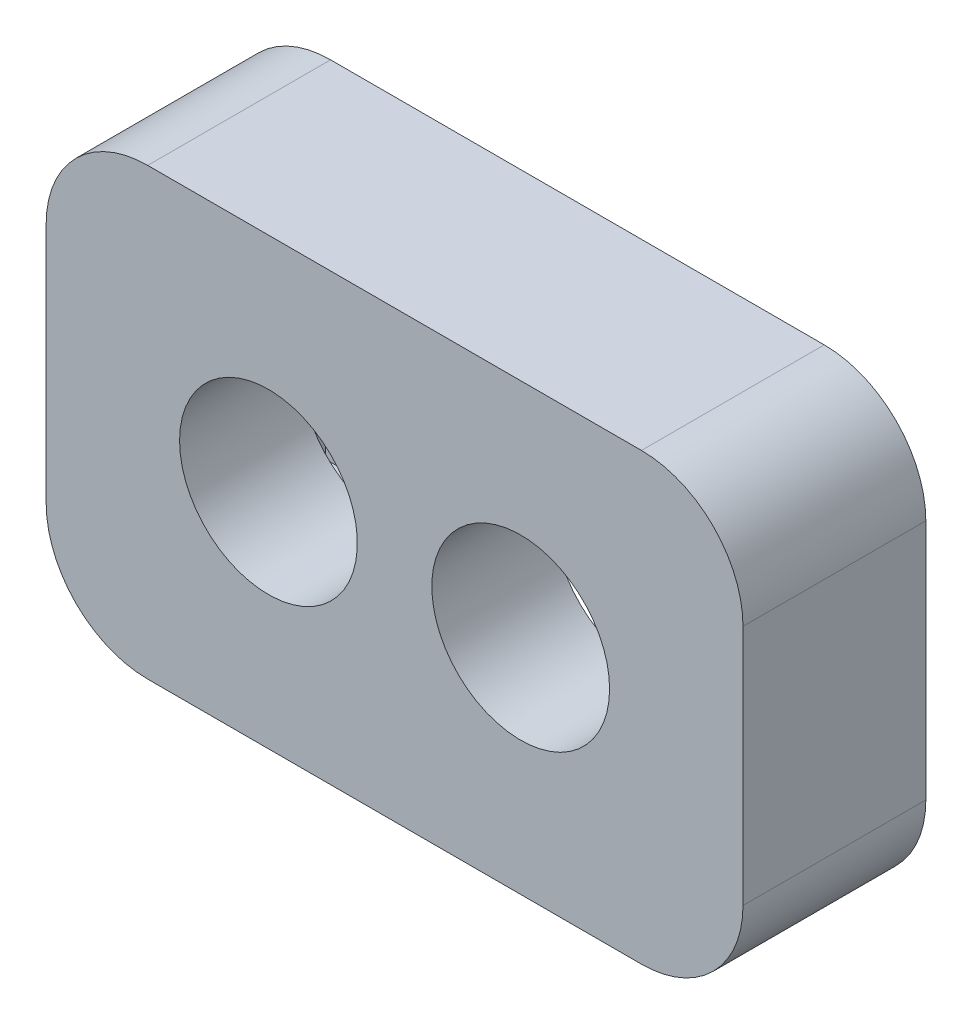
SolidWorks part; units mm, degrees
ref_plane "Front Plane" through (0, 0, 0) normal (0, 0, 1) x (1, 0, 0)
ref_plane "Top Plane" through (0, 0, 0) normal (0, 1, 0) x (1, 0, 0)
ref_plane "Right Plane" through (0, 0, 0) normal (1, 0, 0) x (0, 0, -1)
sketch "Sketch1" plane through (0, 0, 0) normal (0, 0, 1) x (1, 0, 0)
  line L0 (-22.8, 10.4) -> (-22.8, -10.4) construction
  line L1 (-34.3, -21.9) -> (34.3, -21.9)
  line L2 (-34.3, -21.9) -> (-34.3, 21.9)
  line L3 (-34.3, 21.9) -> (34.3, 21.9)
  line L4 (34.3, -21.9) -> (34.3, 21.9)
  line L5 (-34.3, -21.9) -> (34.3, 21.9) construction
  line L6 (-34.3, 21.9) -> (34.3, -21.9) construction
  line L7 (-22.8, -10.4) -> (22.8, -10.4) construction
  line L8 (0, 15.7444) -> (0, -21.2968) construction
  circle A1 centre (12.416, 0) radius 8.75
  circle A2 centre (-12.416, 0) radius 8.75
  point P0 (0, 0)
  dimension "D3" = 17.5
  dimension "D1" = 11.5
  dimension "D2" = 11.5
extrude "Boss-Extrude1" add sketch "Sketch1" along a picked direction on the side of the normal blind 12
sketch "Sketch2" plane through (0, 0, 0) normal (0, 0, -1) x (-1, 0, 0)
  line L0 (3.175, 6) -> (-3.175, 6) construction
  line L1 (-3.175, 10.25) -> (3.175, 10.25) construction
  line L2 (3.175, 6) -> (-3.175, 6)
  line L3 (-3.175, 10.25) -> (3.175, 10.25)
  arc A0 (-3.175, 10.25) -> (-3.175, 6) centre (-3.175, 8.125) ccw construction
  arc A1 (3.175, 6) -> (3.175, 10.25) centre (3.175, 8.125) ccw construction
  arc A2 (-3.175, 10.25) -> (-3.175, 6) centre (-3.175, 8.125) ccw
  arc A3 (3.175, 6) -> (3.175, 10.25) centre (3.175, 8.125) ccw
extrude "Cut-Extrude1" cut sketch "Sketch2" against normal up to vertex (3.35 mm away)
sketch "Sketch3" plane through (0, 0, 0) normal (0, 0, -1) x (-1, 0, 0)
  line L0 (22.8, -10.4) -> (-22.8, -10.4) construction
  line L1 (-22.8, -10.4) -> (-22.8, 10.4) construction
  line L2 (-22.8, 10.4) -> (22.8, 10.4) construction
  line L3 (22.8, 10.4) -> (22.8, -10.4) construction
  line L4 (22.8, -10.4) -> (-22.8, -10.4)
  line L5 (-22.8, -10.4) -> (-22.8, 10.4)
  line L6 (-22.8, 10.4) -> (22.8, 10.4)
  line L7 (22.8, 10.4) -> (22.8, -10.4)
  line L8 (34.3, -21.9) -> (-34.3, -21.9) construction
  line L9 (-34.3, -21.9) -> (-34.3, 21.9) construction
  line L10 (-34.3, 21.9) -> (34.3, 21.9) construction
  line L11 (34.3, 21.9) -> (34.3, -21.9) construction
  line L12 (34.3, -21.9) -> (-34.3, -21.9)
  line L13 (-34.3, -21.9) -> (-34.3, 21.9)
  line L14 (-34.3, 21.9) -> (34.3, 21.9)
  line L15 (34.3, 21.9) -> (34.3, -21.9)
extrude "Boss-Extrude2" add sketch "Sketch3" along normal blind 6
fillet "Fillet1" radius 10 4 edges at (34.3, 21.9, 3) (34.3, -21.9, 3) (-34.3, -21.9, 3) (-34.3, 21.9, 3)
sketch "Sketch4" plane through (0, 0, -6) normal (0, 0, -1) x (-1, 0, 0)
  line L0 (0, 23.8651) -> (0, -24.5579) construction
  line L1 (0, 0) -> (-37.2603, 0) construction
  circle A0 centre (27, 14.6) radius 5.2
  circle A1 centre (-27, 14.6) radius 5.2
  circle A2 centre (27, -14.6) radius 5.2
  circle A3 centre (-27, -14.6) radius 5.2
  dimension "D1" = 10.4
  dimension "D2" = 7.3
  dimension "D3" = 7.3
extrude "Cut-Extrude2" cut sketch "Sketch4" against normal blind 2.3
sketch "Sketch6" plane through (0, 0, -6) normal (0, 0, -1) x (-1, 0, 0)
  line L0 (-22.8, -10.4) -> (22.8, -10.4) construction
  line L1 (-22.8, 10.4) -> (-22.8, -10.4) construction
  line L2 (22.8, 10.4) -> (-22.8, 10.4) construction
  line L3 (22.8, -10.4) -> (22.8, 10.4) construction
  line L4 (-22.8, -10.4) -> (-7.275, -10.4)
  line L5 (-22.8, 10.4) -> (-22.8, -10.4)
  line L6 (22.8, 10.4) -> (-22.8, 10.4)
  line L7 (22.8, -10.4) -> (22.8, 10.4)
  line L8 (-21.8, -9.4) -> (-7.275, -9.4)
  line L9 (21.8, -9.4) -> (21.8, 9.4)
  line L10 (21.8, 9.4) -> (-21.8, 9.4)
  line L11 (-21.8, 9.4) -> (-21.8, -9.4)
  line L12 (-7.275, -7.95) -> (-7.275, -10.3) construction
  line L13 (7.275, -10.3) -> (7.275, -7.95) construction
  line L14 (-7.275, -9.4) -> (-7.275, -10.4)
  line L15 (7.275, -10.4) -> (7.275, -9.4)
  line L16 (7.275, -9.4) -> (21.8, -9.4)
  line L17 (7.275, -10.4) -> (22.8, -10.4)
  line L18 (-21.8, -9.4) -> (21.8, -9.4) construction
  line L20 (-22.8, -10.4) -> (22.8, -10.4) construction
  point P14 (7.275, -10.4)
  point P16 (-7.275, -10.4)
  dimension "D1" = 1
extrude "Boss-Extrude6" add sketch "Sketch6" against normal blind 2
fillet "Fillet2" radius 3 4 edges at (-21.8, -9.4, -5) (-21.8, 9.4, -5) (21.8, -9.4, -5) (21.8, 9.4, -5)
fillet "Fillet3" radius 1 9 edges at (13.0375, -9.4, -4) (20.9213, -8.5213, -4) (21.8, 0, -4) (20.9213, 8.5213, -4) (0, 9.4, -4) (-20.9213, 8.5213, -4) (-13.0375, -9.4, -4) (-20.9213, -8.5213, -4) (-21.8, 0, -4)
sketch "Sketch7" plane through (0, 0, -6) normal (0, 0, -1) x (-1, 0, 0)
  line L0 (-24.3, -21.9) -> (24.3, -21.9) construction
  line L1 (7.275, -10.4) -> (-7.275, -10.4)
  line L2 (7.275, -10.4) -> (7.275, -21.9)
  line L3 (7.275, -21.9) -> (-7.275, -21.9)
  line L4 (-7.275, -10.4) -> (-7.275, -21.9)
extrude "Cut-Extrude3" cut sketch "Sketch7" against normal blind 5
